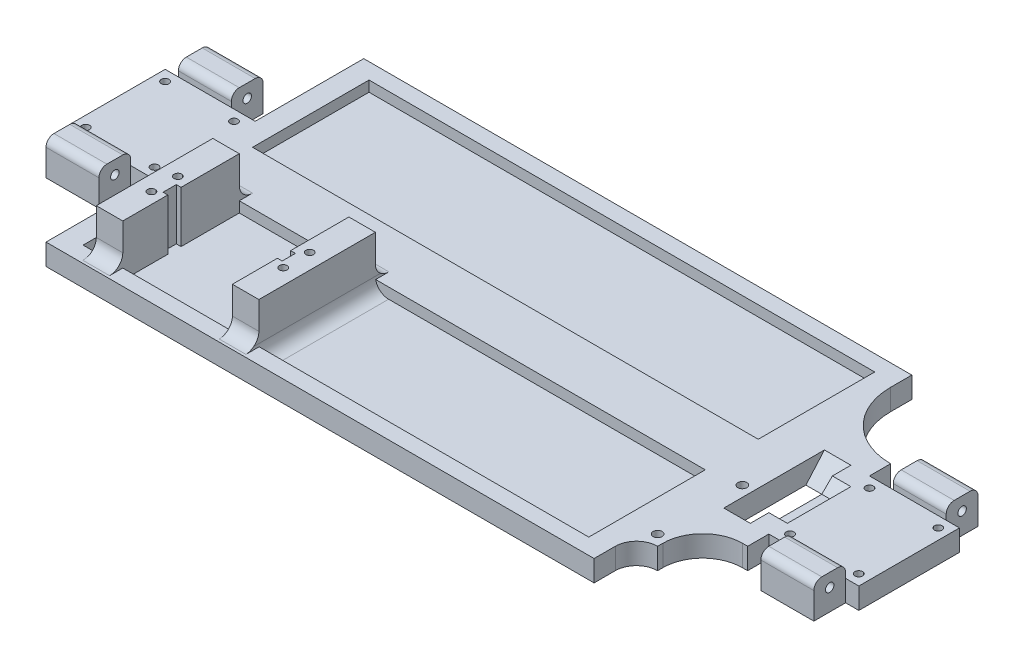
SolidWorks part; units mm, degrees
ref_plane "Front" through (0, 0, 0) normal (0, 0, 1) x (1, 0, 0)
ref_plane "Top" through (0, 0, 0) normal (0, 1, 0) x (1, 0, 0)
ref_plane "Right" through (0, 0, 0) normal (1, 0, 0) x (0, 0, -1)
sketch "Sketch1" plane through (0, 0, 0) normal (0, 1, 0) x (1, 0, 0)
  line L1 (0, 0) -> (300, 0)
  line L2 (0, 0) -> (0, -20)
  line L3 (0, -20) -> (300, -20)
  line L4 (300, 0) -> (300, -20)
  dimension "D1" = 20
  dimension "D2" = 300
extrude "Boss-Extrude1" add sketch "Sketch1" along normal blind 8
sketch "Sketch2" plane through (0, 0, 20) normal (0, 0, 1) x (1, 0, 0)
  line L0 (0, 8) -> (300, 8) construction
  line L1 (0, 0) -> (34, 0)
  line L2 (0, 0) -> (0, 8)
  line L3 (0, 8) -> (34, 8)
  line L4 (34, 0) -> (34, 8)
  line L5 (266, 8) -> (300, 8)
  line L6 (300, 0) -> (300, 8)
  line L7 (266, 0) -> (300, 0)
  line L8 (266, 0) -> (266, 8)
  dimension "D1" = 34
  dimension "D2" = 2
extrude "Boss-Extrude2" add sketch "Sketch2" along normal blind 9
sketch "Sketch3" plane through (0, 0, 0) normal (0, 0, -1) x (-1, 0, 0)
  line L0 (-300, 8) -> (0, 8) construction
  line L1 (0, 0) -> (-34, 0)
  line L2 (0, 0) -> (0, 8)
  line L3 (0, 8) -> (-34, 8)
  line L4 (-34, 0) -> (-34, 8)
  line L5 (-300, 0) -> (-300, 8)
  line L6 (-266, 8) -> (-300, 8)
  line L7 (-266, 0) -> (-266, 8)
  line L8 (-266, 0) -> (-300, 0)
  dimension "D1" = 34
  dimension "D2" = 2
extrude "Boss-Extrude3" add sketch "Sketch3" along normal blind 9
sketch "Sketch4" plane through (0, 8, 0) normal (0, 1, 0) x (1, 0, 0)
  line L0 (0, 9) -> (34, 9) construction
  line L1 (0, 9) -> (0, -29) construction
  circle A0 centre (4, 5) radius 1.45
  circle A1 centre (30, 5) radius 1.45
  circle A2 centre (30, -25) radius 1.45
  circle A3 centre (4, -25) radius 1.45
  circle A4 centre (296, -25) radius 1.45
  circle A5 centre (296, 5) radius 1.45
  circle A6 centre (270, -25) radius 1.45
  circle A7 centre (270, 5) radius 1.45
  dimension "D1" = 2.9
  dimension "D2" = 4
  dimension "D3" = 4
  dimension "D4" = 2
  dimension "D5" = 2
  dimension "D6" = 2
extrude "Cut-Extrude1" cut sketch "Sketch4" against normal through all
sketch "Sketch5" plane through (0, 0, 20) normal (0, 0, 1) x (1, 0, 0)
  line L0 (34, 8) -> (266, 8) construction
  line L1 (266, 0) -> (241, 0)
  line L2 (266, 0) -> (266, 8)
  line L3 (266, 8) -> (241, 8)
  line L4 (241, 0) -> (241, 8)
  dimension "D1" = 25
extrude "Boss-Extrude4" add sketch "Sketch5" along normal blind 17
sketch "Sketch6" plane through (0, 0, 0) normal (0, 0, -1) x (-1, 0, 0)
  line L0 (-266, 0) -> (-34, 0) construction
  line L1 (-266, 8) -> (-241, 8)
  line L2 (-266, 8) -> (-266, 0)
  line L3 (-266, 0) -> (-241, 0)
  line L4 (-241, 8) -> (-241, 0)
  dimension "D1" = 25
extrude "Boss-Extrude5" add sketch "Sketch6" along normal blind 17
sketch "Sketch7" plane through (0, 8, 0) normal (0, 1, 0) x (1, 0, 0)
  line L0 (266, -37) -> (241, -37) construction
  line L1 (259, -29) -> (249, -29)
  line L2 (259, -29) -> (259, 9)
  line L3 (259, 9) -> (249, 9)
  line L4 (249, -29) -> (249, 9)
  line L5 (241, -37) -> (241, -20) construction
  dimension "D1" = 10
  dimension "D2" = 38
  dimension "D3" = 8
  dimension "D4" = 8
extrude "Cut-Extrude2" cut sketch "Sketch7" against normal through all
sketch "Sketch8" plane through (0, 8, 0) normal (0, 1, 0) x (1, 0, 0)
  line L0 (259, -29) -> (259, 9) construction
  line L1 (259, -18) -> (266, -18)
  line L2 (259, -18) -> (259, -2)
  line L3 (259, -2) -> (266, -2)
  line L4 (266, -18) -> (266, -2)
  line L5 (266, -37) -> (241, -37) construction
  dimension "D1" = 7
  dimension "D2" = 16
  dimension "D3" = 19
extrude "Cut-Extrude3" cut sketch "Sketch8" against normal blind 4
sketch "Sketch9" plane through (259, 0, 0) normal (-1, 0, 0) x (0, 0, 1)
  line L0 (18, 4) -> (22, 8)
  line L1 (29, 8) -> (18, 8) construction
  line L2 (22, 8) -> (18, 8)
  line L3 (18, 8) -> (18, 4)
  line L4 (2, 4) -> (-2, 8)
  line L5 (2, 8) -> (-9, 8) construction
  line L6 (-2, 8) -> (2, 8)
  line L7 (2, 8) -> (2, 4)
  dimension "D1" = 4
  dimension "D2" = 4
extrude "Cut-Extrude4" cut sketch "Sketch9" against normal blind 7
sketch "Sketch10" plane through (259, 0, 0) normal (-1, 0, 0) x (0, 0, 1)
  line L0 (-9, 8) -> (-2, 0)
  line L1 (29, 0) -> (-9, 0) construction
  line L2 (-2, 0) -> (-9, 0)
  line L3 (-9, 0) -> (-9, 8)
  line L4 (29, 8) -> (22, 0)
  line L5 (22, 0) -> (29, 0)
  line L6 (29, 0) -> (29, 8)
  line L7 (-51.4523, 12.1971) -> (-51.8778, 12.5861)
  line M6 (-9, 8) -> (-9, 0)
  line M7 (-9, 0) -> (29, 0)
  line M8 (29, 0) -> (29, 8)
  dimension "D1" = 7
  dimension "D2" = 7
extrude "Boss-Extrude6" add sketch "Sketch10" along normal blind 10 contours L0 M6 M7 | L4 M8 M7 region at (259, 2.6667, 26.6667) region at (259, 2.6667, -6.6667)
sketch "Sketch12" plane through (0, 0, 37) normal (0, 0, 1) x (1, 0, 0)
  line L0 (241, 0) -> (266, 0) construction
  line L1 (241, 8) -> (249, 8)
  line L2 (241, 8) -> (241, 0)
  line L3 (241, 0) -> (249, 0)
  line L4 (249, 8) -> (249, 0)
  dimension "D1" = 8
extrude "Boss-Extrude7" add sketch "Sketch12" along normal blind 17
sketch "Sketch13" plane through (0, 8, 0) normal (0, 1, 0) x (1, 0, 0)
  line L0 (249, -54) -> (241, -54) construction
  line L1 (249, -54) -> (249, -37) construction
  circle A0 centre (245, -50) radius 1.7
  circle A1 centre (245, -18) radius 1.7
  dimension "D1" = 3.4
  dimension "D2" = 4
  dimension "D3" = 4
  dimension "D4" = 2
extrude "Cut-Extrude6" cut sketch "Sketch13" against normal through all
sketch "Sketch14" plane through (0, 0, 29) normal (0, 0, 1) x (1, 0, 0)
  line L1 (295, 13) -> (275, 13)
  line L2 (295, 13) -> (295, 0)
  line L3 (295, 0) -> (275, 0)
  line L4 (275, 13) -> (275, 0)
  line L5 (266, 0) -> (300, 0) construction
  line L7 (266, 8) -> (266, 0) construction
  dimension "D1" = 20
  dimension "D2" = 9
  dimension "D3" = 13
extrude "Boss-Extrude8" add sketch "Sketch14" along normal blind 12
sketch "Sketch15" plane through (295, 0, 0) normal (1, 0, 0) x (0, 0, -1)
  line L0 (-41, 0) -> (-41, 13) construction
  line L1 (-41, 13) -> (-29, 13) construction
  circle A0 centre (-35, 8) radius 1.6
  dimension "D1" = 3.2
  dimension "D2" = 6
  dimension "D3" = 5
extrude "Cut-Extrude7" cut sketch "Sketch15" against normal blind 20
sketch "Sketch16" plane through (0, 0, -9) normal (0, 0, -1) x (-1, 0, 0)
  line L1 (-295, 13) -> (-275, 13)
  line L2 (-295, 13) -> (-295, 0)
  line L3 (-295, 0) -> (-275, 0)
  line L4 (-275, 13) -> (-275, 0)
  line L5 (-300, 0) -> (-266, 0) construction
  line L6 (-266, 0) -> (-266, 8) construction
  dimension "D1" = 20
  dimension "D2" = 9
  dimension "D3" = 13
extrude "Boss-Extrude9" add sketch "Sketch16" along normal blind 12
sketch "Sketch17" plane through (295, 0, 0) normal (1, 0, 0) x (0, 0, -1)
  line L1 (21, 13) -> (21, 0) construction
  line L2 (21, 13) -> (9, 13) construction
  circle A0 centre (15, 8) radius 1.6
  dimension "D1" = 3.2
  dimension "D2" = 5
  dimension "D3" = 6
extrude "Cut-Extrude8" cut sketch "Sketch17" against normal blind 20
sketch "Sketch18" plane through (0, 0, -9) normal (0, 0, -1) x (-1, 0, 0)
  line L1 (-25, 13) -> (-5, 13)
  line L2 (-25, 13) -> (-25, 0)
  line L3 (-25, 0) -> (-5, 0)
  line L4 (-5, 13) -> (-5, 0)
  line L5 (-34, 0) -> (0, 0) construction
  line L6 (-34, 8) -> (-34, 0) construction
  dimension "D1" = 20
  dimension "D2" = 9
  dimension "D3" = 13
extrude "Boss-Extrude10" add sketch "Sketch18" along normal blind 12
sketch "Sketch19" plane through (5, 0, 0) normal (-1, 0, 0) x (0, 0, 1)
  line L0 (-21, 0) -> (-21, 13) construction
  line L1 (-21, 13) -> (-9, 13) construction
  circle A0 centre (-15, 8) radius 1.6
  dimension "D1" = 3.2
  dimension "D2" = 6
  dimension "D3" = 5
extrude "Cut-Extrude9" cut sketch "Sketch19" against normal blind 20
sketch "Sketch20" plane through (0, 0, 29) normal (0, 0, 1) x (1, 0, 0)
  line L1 (5, 13) -> (25, 13)
  line L2 (5, 13) -> (5, 0)
  line L3 (5, 0) -> (25, 0)
  line L4 (25, 13) -> (25, 0)
  line L5 (0, 0) -> (34, 0) construction
  line L6 (34, 0) -> (34, 8) construction
  dimension "D1" = 20
  dimension "D2" = 9
  dimension "D3" = 13
extrude "Boss-Extrude11" add sketch "Sketch20" along normal blind 12
sketch "Sketch21" plane through (5, 0, 0) normal (-1, 0, 0) x (0, 0, 1)
  line L0 (41, 13) -> (41, 0) construction
  line L2 (41, 13) -> (29, 13) construction
  circle A0 centre (35, 8) radius 1.6
  dimension "D1" = 3.2
  dimension "D2" = 6
  dimension "D3" = 5
extrude "Cut-Extrude10" cut sketch "Sketch21" against normal blind 20
sketch "Sketch22" plane through (0, 0, 0) normal (0, -1, 0) x (-1, 0, 0)
  line L0 (-34, -20) -> (-241, -20) construction
  line L1 (-34, -20) -> (-241, -20)
  line L2 (-34, -20) -> (-34, -70)
  line L3 (-34, -70) -> (-241, -70)
  line L4 (-241, -20) -> (-241, -70)
  line L5 (-34, 9) -> (-34, 0) construction
  line L6 (-34, 0) -> (-241, 0)
  line L7 (-34, 0) -> (-34, 50)
  line L8 (-34, 50) -> (-241, 50)
  line L9 (-241, 0) -> (-241, 50)
  line L10 (-241, 0) -> (-34, 0) construction
  dimension "D1" = 50
  dimension "D2" = 50
extrude "Boss-Extrude12" add sketch "Sketch22" against normal blind 8
sketch "Sketch23" plane through (0, 8, 0) normal (0, 1, 0) x (1, 0, 0)
  line L0 (241, -70) -> (34, -70) construction
  line L1 (233, -64) -> (42, -64)
  line L2 (233, -64) -> (233, -20)
  line L3 (233, -20) -> (42, -20)
  line L4 (42, -64) -> (42, -20)
  line L5 (233, 44) -> (42, 44)
  line L6 (233, 44) -> (233, 0)
  line L7 (233, 0) -> (42, 0)
  line L8 (42, 44) -> (42, 0)
  line L9 (241, -54) -> (241, -70) construction
  line L10 (34, -70) -> (34, -29) construction
  line L11 (34, 9) -> (34, 50) construction
  line L12 (34, 50) -> (241, 50) construction
  line L13 (241, 50) -> (241, 17) construction
  dimension "D1" = 6
  dimension "D2" = 8
  dimension "D3" = 8
  dimension "D4" = 44
  dimension "D5" = 8
  dimension "D6" = 44
  dimension "D7" = 6
  dimension "D8" = 8
extrude "Cut-Extrude11" cut sketch "Sketch23" against normal blind 4
sketch "Sketch24" plane through (0, 4, 0) normal (0, 1, 0) x (1, 0, 0)
  line L0 (233, -20) -> (42, -20) construction
  line L1 (98.4, -20) -> (108.4, -20)
  line L2 (98.4, -20) -> (98.4, -64)
  line L3 (98.4, -64) -> (108.4, -64)
  line L4 (108.4, -20) -> (108.4, -64)
  line L5 (42, -64) -> (233, -64) construction
  line L7 (42, -20) -> (42, -64) construction
  line L8 (42, -20) -> (42, -64) construction
  line L9 (47, -20) -> (57, -20)
  line L10 (47, -20) -> (47, -64)
  line L11 (47, -64) -> (57, -64)
  line L12 (57, -20) -> (57, -64)
  dimension "D1" = 10
  dimension "D2" = 56.4
  dimension "D3" = 10
  dimension "D4" = 5
extrude "Boss-Extrude14" add sketch "Sketch24" along normal blind 19.4
sketch "Sketch25" plane through (0, 23.4, 0) normal (0, 1, 0) x (1, 0, 0)
  line L2 (47, -64) -> (57, -64) construction
  line L4 (98.4, -20) -> (98.4, -64) construction
  line L5 (98.4, -64) -> (108.4, -64) construction
  line L6 (57, -64) -> (57, -20) construction
  circle A0 centre (102.6, -49) radius 1.45
  circle A1 centre (102.6, -39) radius 1.45
  circle A2 centre (52.8, -49) radius 1.45
  circle A3 centre (52.8, -39) radius 1.45
  dimension "D1" = 2.9
  dimension "D2" = 2.9
  dimension "D3" = 2.9
  dimension "D4" = 2.9
  dimension "D5" = 10
  dimension "D6" = 10
  dimension "D7" = 4.2
  dimension "D8" = 4.2
  dimension "D9" = 15
  dimension "D10" = 4.2
  dimension "D11" = 4.2
  dimension "D12" = 15
extrude "Cut-Extrude12" cut sketch "Sketch25" against normal blind 15
fillet "Fillet1" radius 5 4 edges at (52, 8, 20) (103.4, 8, 20) (103.4, 8, 64) (52, 8, 64)
fillet "Fillet2" radius 5 2 edges at (47, 4, 42) (108.4, 4, 42)
fillet "Fillet3" radius 8 1 edges at (241, 4, 54)
fillet "Fillet4" radius 15 1 edges at (249, 4, 37)
fillet "Fillet5" radius 25 1 edges at (241, 4, -17)
fillet "Fillet6" radius 3 8 edges at (15, 13, 41) (15, 13, 29) (15, 13, -9) (15, 13, -21) (285, 13, 41) (285, 13, 29) (285, 13, -9) (285, 13, -21)
sketch "Sketch27" plane through (0, 23.4, 0) normal (0, 1, 0) x (1, 0, 0)
  line L0 (57, -64) -> (57, -20) construction
  line L1 (57, -47) -> (55.2, -47)
  line L2 (57, -47) -> (57, -42)
  line L3 (57, -42) -> (55.2, -42)
  line L4 (55.2, -47) -> (55.2, -42)
  line L5 (98.4, -20) -> (98.4, -64) construction
  line L6 (98.4, -47) -> (100.2, -47)
  line L7 (98.4, -47) -> (98.4, -42)
  line L8 (98.4, -42) -> (100.2, -42)
  line L9 (100.2, -47) -> (100.2, -42)
  line L10 (98.4, -64) -> (108.4, -64) construction
  line L11 (47, -64) -> (57, -64) construction
  dimension "D1" = 5
  dimension "D2" = 5
  dimension "D3" = 1.8
  dimension "D4" = 1.8
  dimension "D5" = 17
  dimension "D6" = 17
extrude "Cut-Extrude13" cut sketch "Sketch27" against normal blind 19.4
